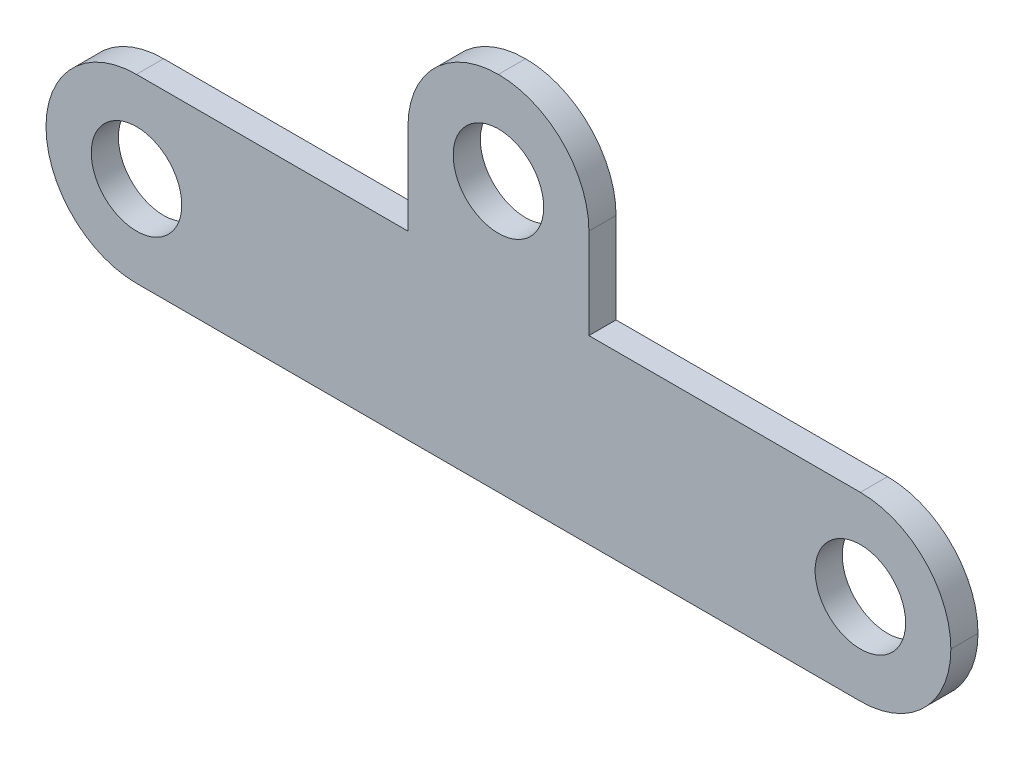
SolidWorks part; units mm, degrees
ref_plane "正面" through (0, 0, 0) normal (0, 0, 1) x (1, 0, 0)
ref_plane "平面" through (0, 0, 0) normal (0, 1, 0) x (1, 0, 0)
ref_plane "右側面" through (0, 0, 0) normal (1, 0, 0) x (0, 0, -1)
sketch "ｽｹｯﾁ1" plane through (0, 0, 0) normal (0, 0, 1) x (1, 0, 0)
  line L1 (0, 0) -> (100, 0)
  line L2 (0, 0) -> (0, 20)
  line L3 (0, 20) -> (100, 20)
  line L4 (100, 0) -> (100, 20)
  dimension "D1" = 100
  dimension "D2" = 20
extrude "ﾎﾞｽ - 押し出し1" add sketch "ｽｹｯﾁ1" along normal blind 3
fillet "ﾌｨﾚｯﾄ1" radius 10 4 edges at (100, 0, 1.5) (100, 20, 1.5) (0, 0, 1.5) (0, 20, 1.5)
sketch "ｽｹｯﾁ4" plane through (0, 20, 0) normal (0, 1, 0) x (1, 0, 0)
  line L0 (90, -3) -> (10, -3) construction
  line L1 (40, -3) -> (60, -3)
  line L2 (40, -3) -> (40, 0)
  line L3 (40, 0) -> (60, 0)
  line L4 (60, -3) -> (60, 0)
  line L5 (90, 0) -> (10, 0) construction
  line L6 (10, 0) -> (10, -3) construction
  dimension "D1" = 30
  dimension "D2" = 20
extrude "ﾎﾞｽ - 押し出し2" add sketch "ｽｹｯﾁ4" along normal blind 20
fillet "ﾌｨﾚｯﾄ2" radius 10 2 edges at (40, 40, 1.5) (60, 40, 1.5)
sketch "ｽｹｯﾁ5" plane through (0, 0, 3) normal (0, 0, 1) x (1, 0, 0)
  line L0 (40, 30) -> (40, 20) construction
  line L1 (40, 20) -> (10, 20) construction
  line L2 (90, 20) -> (60, 20) construction
  circle A0 centre (50, 29.7844) radius 5
  circle A1 centre (10, 10) radius 5
  circle A2 centre (90, 10) radius 5
  dimension "D2" = 10
  dimension "D7" = 10
  dimension "D8" = 10
  dimension "D1" = 10
  dimension "D3" = 10
  dimension "D4" = 10
  dimension "D5" = 10
  dimension "D6" = 10
extrude "ｶｯﾄ - 押し出し1" cut sketch "ｽｹｯﾁ5" against normal blind 10 contours A1
extrude "ｶｯﾄ - 押し出し2" cut sketch "ｽｹｯﾁ5<3>" against normal blind 10
sketch "ｽｹｯﾁ5<3>" plane through (0, 0, 3) normal (0, 0, 1) x (1, 0, 0) same geometry as "ｽｹｯﾁ5"
